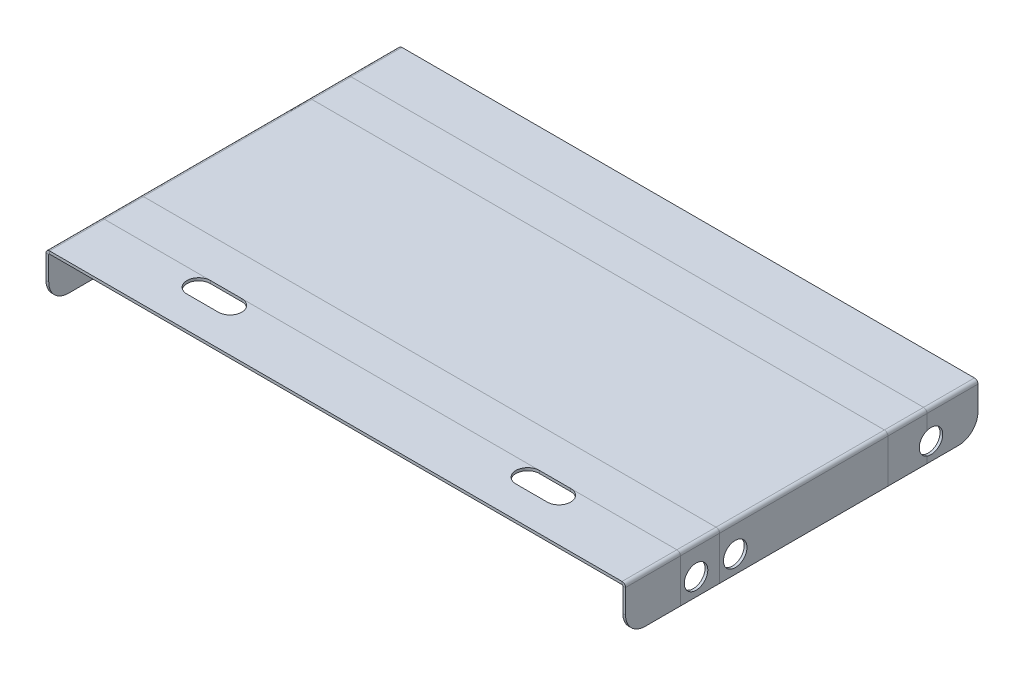
SolidWorks part; units mm, degrees
note: The reader was unsure of these and kept them because the rebuilt part matched: flange length of "边线-法兰1".
ref_plane "前视基准面" through (0, 0, 0) normal (0, 0, 1) x (1, 0, 0)
ref_plane "上视基准面" through (0, 0, 0) normal (0, 1, 0) x (1, 0, 0)
ref_plane "右视基准面" through (0, 0, 0) normal (1, 0, 0) x (0, 0, -1)
sketch "草图1" plane through (0, 0, 0) normal (0, 1, 0) x (1, 0, 0)
  line L0 (-46, -34) -> (-38, -34) construction
  line L1 (-74, 45) -> (74, 45)
  line L2 (-74, 45) -> (-74, -45)
  line L3 (-74, -45) -> (74, -45)
  line L4 (74, 45) -> (74, -45)
  line L5 (-74, 45) -> (74, -45) construction
  line L6 (-74, -45) -> (74, 45) construction
  line L7 (-46, -31) -> (-38, -31)
  line L8 (-46, -37) -> (-38, -37)
  line L9 (38, -34) -> (46, -34) construction
  line L10 (38, -31) -> (46, -31)
  line L11 (38, -37) -> (46, -37)
  arc A0 (-46, -31) -> (-46, -37) centre (-46, -34) ccw
  arc A1 (-38, -37) -> (-38, -31) centre (-38, -34) ccw
  arc A2 (38, -31) -> (38, -37) centre (38, -34) ccw
  arc A3 (46, -37) -> (46, -31) centre (46, -34) ccw
  point P0 (0, 0)
  point P8 (-42, -34)
  point P13 (42, -34)
  point P20 (-42, -37)
  dimension "D7" = 28
  dimension "D8" = 28
  dimension "D1" = 148
  dimension "D2" = 90
  dimension "D3" = 8
  dimension "D4" = 8
  dimension "D5" = 6
  dimension "D6" = 6
  dimension "D9" = 8
base flange "基体-法兰1" sketch "草图1" thickness 0.7 reverse thickness direction no parameters "D1"=0.2
edge flange "边线-法兰1" sketch "草图12" flange profiles "草图12", "草图13" flange angle 90 flange length 12 flange position material inside bend radius 0.2 thickness 0.7 relief rectangular parameters "D6"=10, "D8"=1
sketch "草图12" plane through (74, -0.7, 0) normal (1, 0, 0) x (0, 0, 1)
  line L2 (-45, 0) -> (-45, 11.3)
  line L3 (-45, 11.3) -> (45, 11.3)
  line L4 (45, 11.3) -> (45, 0)
  line L7 (45, 0) -> (-45, 0) construction
  line L8 (45, 0) -> (-45, 0)
  line L9 (45, -0.7) -> (-45, -0.7) construction
  circle A0 centre (-33, 6.8) radius 3
  circle A1 centre (17, 6.8) radius 3
  circle A2 centre (27, 6.8) radius 3
  dimension "D1" = 6
  dimension "D2" = 4.5
  dimension "D3" = 12
  dimension "D4" = 50
  dimension "D5" = 7.5
  dimension "D6" = 10
sketch "草图13" plane through (-74, -0.7, 0) normal (-1, 0, 0) x (0, 0, -1)
  line L2 (-45, 0) -> (-45, 11.3)
  line L3 (-45, 11.3) -> (45, 11.3)
  line L4 (45, 11.3) -> (45, 0)
  line L7 (45, 0) -> (-45, 0) construction
  line L8 (45, 0) -> (-45, 0)
bend "边线折弯1" bend radius 0.2 bend angle 90 parameters "D5"=1
bend "边线折弯2" bend radius 0.2 bend angle 90 parameters "D5"=2
fillet "圆角2" radius 5 4 edges at (73.65, -12, -45) (73.65, -12, 45) (-73.65, -12, 45) (-73.65, -12, -45)
sketch "草图15" plane through (-74, 0, 0) normal (-1, 0, 0) x (0, 0, 1)
  circle A0 centre (-33, -7.5) radius 3
  circle A1 centre (17, -7.5) radius 3
  circle A2 centre (27, -7.5) radius 3
  dimension "D1" = 6
  dimension "D2" = 10
  dimension "D3" = 50
extrude "切除-拉伸1" cut sketch "草图15" against normal blind 10
sketch "草图17" plane through (0, 0, 0) normal (0, 1, 0) x (1, 0, 0)
  line L0 (-74, 32) -> (74, 32)
  line L1 (-74, 45) -> (-74, -45) construction
  line L3 (-73.1, 45) -> (-73.1, -45) construction
  line L4 (-74, -31) -> (74, -31)
  line L5 (74, 45) -> (74, -45) construction
  line L6 (-73.1, 22) -> (74, 22)
  line L7 (-46, -31) -> (-38, -31) construction
  line L8 (-73.1, -21) -> (74, -21)
  line L9 (-73.1, -21) -> (-73.1, -16)
  line L10 (-73.1, -16) -> (-74, -16)
  line L11 (-73.1, 22) -> (-73.1, 17)
  line L12 (-73.1, 17) -> (-74, 17)
  point P12 (-42, -31)
  dimension "D1" = 0
  dimension "D2" = 63
  dimension "D3" = 10
  dimension "D4" = 5
  dimension "D5" = 5
  dimension "D6" = 10
split "分割1" trim tools "草图17" bodies to split 109 resulting bodies 113 114 115 116 117
sketch "折弯-线1" [suppressed] plane through (0, 0, 0) normal (0, 1, 0) x (1, 0, 0)
sketch "边界框1" [suppressed] plane through (0, 0, 0) normal (0, 1, 0) x (1, 0, 0)
sheet metal parameters "钣金6" thickness 0.7 parameters "D1"=0.2
flat pattern "平板型式6" [suppressed]
sketch "折弯-线2" plane through (0, 0, 0) normal (0, 1, 0) x (1, 0, 0)
sketch "边界框2" [suppressed] plane through (0, 0, 0) normal (0, 1, 0) x (1, 0, 0)
sheet metal parameters "钣金7" thickness 0.7 parameters "D1"=0.2
flat pattern "平板型式6" [suppressed]
sketch "折弯-线2" plane through (0, 0, 0) normal (0, 1, 0) x (1, 0, 0)
sketch "边界框2" [suppressed] plane through (0, 0, 0) normal (0, 1, 0) x (1, 0, 0)
bend of the flat pattern "展平-<边线折弯1>1"
bend of the flat pattern "展平-<边线折弯2>1"
sheet metal parameters "钣金9" thickness 0.7 parameters "D1"=0.2
flat pattern "平板型式6" [suppressed]
sketch "折弯-线2" plane through (0, 0, 0) normal (0, 1, 0) x (1, 0, 0)
sketch "边界框2" [suppressed] plane through (0, 0, 0) normal (0, 1, 0) x (1, 0, 0)
bend of the flat pattern "展平-<边线折弯1>1"
bend of the flat pattern "展平-<边线折弯2>1"
sheet metal parameters "钣金13" thickness 0.7 parameters "D1"=0.2
flat pattern "平板型式13"
sketch "折弯-线3" plane through (0, 0, 0) normal (0, 1, 0) x (1, 0, 0)
  line L0 (-74, 45) -> (-74, 32) construction
  line L1 (74, 45) -> (74, 32) construction
  line L2 (-74, 45) -> (-74, 32) construction
  line L3 (74, 45) -> (74, 32) construction
sketch3d "边界框3" [suppressed]
  line L0 (-86, 32, 0) -> (86, 32, 0) construction
  line L1 (-86, 45, 0) -> (86, 45, 0) construction
  line L2 (-86, 32, 0) -> (-86, 45, 0) construction
  line L3 (86, 32, 0) -> (86, 45, 0) construction
bend of the flat pattern "展平-<边线折弯1>2"
bend of the flat pattern "展平-<边线折弯2>2"
sheet metal parameters "钣金14" thickness 0.7 parameters "D1"=0.2
flat pattern "平板型式14"
sketch "折弯-线4" plane through (0, 0, 0) normal (0, 1, 0) x (1, 0, 0)
  line L0 (-74, -45) -> (-74, -31) construction
  line L1 (74, -45) -> (74, -31) construction
  line L2 (-74, -45) -> (-74, -31) construction
  line L3 (74, -45) -> (74, -31) construction
sketch3d "边界框4" [suppressed]
  line L0 (-86, -45, 0) -> (86, -45, 0) construction
  line L1 (-86, -31, 0) -> (86, -31, 0) construction
  line L2 (-86, -45, 0) -> (-86, -31, 0) construction
  line L3 (86, -45, 0) -> (86, -31, 0) construction
bend of the flat pattern "展平-<边线折弯1>3"
bend of the flat pattern "展平-<边线折弯2>3"
sheet metal parameters "钣金15" thickness 0.7 parameters "D1"=0.2
flat pattern "平板型式15"
sketch "折弯-线5" plane through (0, 0, 0) normal (0, 1, 0) x (1, 0, 0)
  line L0 (-74, -16) -> (-74, 17) construction
  line L1 (74, -21) -> (74, 22) construction
  line L2 (-74, -16) -> (-74, 17) construction
  line L3 (74, -21) -> (74, 22) construction
sketch3d "边界框5" [suppressed]
  line L0 (86, -21, 0) -> (-86, -21, 0) construction
  line L1 (86, 22, 0) -> (-86, 22, 0) construction
  line L2 (86, -21, 0) -> (86, 22, 0) construction
  line L3 (-86, -21, 0) -> (-86, 22, 0) construction
bend of the flat pattern "展平-<边线折弯1>4"
bend of the flat pattern "展平-<边线折弯2>4"
sheet metal parameters "钣金16" thickness 0.7 parameters "D1"=0.2
flat pattern "平板型式16"
sketch "折弯-线6" plane through (0, 0, 0) normal (0, 1, 0) x (1, 0, 0)
  line L0 (-74, 17) -> (-74, 32) construction
  line L1 (74, 22) -> (74, 32) construction
  line L2 (-74, 17) -> (-74, 32) construction
  line L3 (74, 22) -> (74, 32) construction
sketch3d "边界框6" [suppressed]
  line L0 (86, 17, 0) -> (-86, 17, 0) construction
  line L1 (86, 32, 0) -> (-86, 32, 0) construction
  line L2 (86, 17, 0) -> (86, 32, 0) construction
  line L3 (-86, 17, 0) -> (-86, 32, 0) construction
bend of the flat pattern "展平-<边线折弯1>5"
bend of the flat pattern "展平-<边线折弯2>5"
sheet metal parameters "钣金17" thickness 0.7 parameters "D1"=0.2
flat pattern "平板型式17"
sketch "折弯-线7" plane through (0, 0, 0) normal (0, 1, 0) x (1, 0, 0)
  line L0 (-74, -31) -> (-74, -16) construction
  line L1 (74, -31) -> (74, -21) construction
  line L2 (-74, -31) -> (-74, -16) construction
  line L3 (74, -31) -> (74, -21) construction
sketch3d "边界框7" [suppressed]
  line L0 (86, -31, 0) -> (-86, -31, 0) construction
  line L1 (86, -16, 0) -> (-86, -16, 0) construction
  line L2 (86, -31, 0) -> (86, -16, 0) construction
  line L3 (-86, -31, 0) -> (-86, -16, 0) construction
bend of the flat pattern "展平-<边线折弯1>6"
bend of the flat pattern "展平-<边线折弯2>6"
